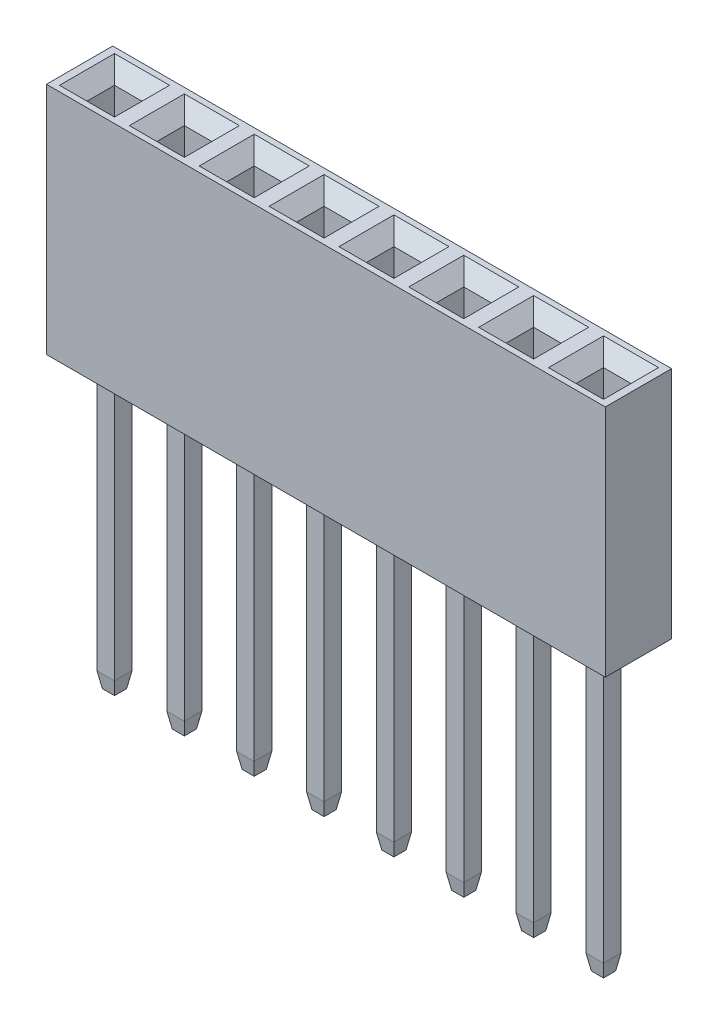
SolidWorks part; units mm, degrees
material "PA Type 6"
ref_plane "Front Plane" through (0, 0, 0) normal (0, 0, 1) x (1, 0, 0)
ref_plane "Top Plane" through (0, 0, 0) normal (0, 1, 0) x (1, 0, 0)
ref_plane "Right Plane" through (0, 0, 0) normal (1, 0, 0) x (0, 0, -1)
ref_plane "Plane1" through (0, -1.65, 0) normal (0, 1, 0) x (1, 0, 0)
sketch "Sketch2" plane through (0, 0, 0) normal (0, 1, 0) x (1, 0, 0)
  line L0 (0, -55) -> (0, 55) construction
  line L1 (-1.27, 1.205) -> (19.05, 1.205)
  line L2 (-1.27, 1.205) -> (-1.27, -1.205)
  line L3 (-1.27, -1.205) -> (19.05, -1.205)
  line L4 (19.05, 1.205) -> (19.05, -1.205)
  line L5 (-55, 0) -> (55, 0) construction
  dimension "D1" = 20.32
  dimension "D2" = 1.27
  dimension "D3" = 2.41
  dimension "D4" = 1.205
extrude "Boss-Extrude1" add sketch "Sketch2" along normal blind 8.51
sketch "Sketch5" plane through (0, 8.51, 0) normal (0, 1, 0) x (1, 0, 0)
  line L0 (-55, 0) -> (55, 0) construction
  line L1 (0.5, 0.5) -> (-0.5, 0.5)
  line L2 (0.5, 0.5) -> (0.5, -0.5)
  line L3 (0.5, -0.5) -> (-0.5, -0.5)
  line L4 (-0.5, 0.5) -> (-0.5, -0.5)
  line L5 (0, -55) -> (0, 55) construction
  dimension "D1" = 0.5
  dimension "D2" = 1
  dimension "D3" = 0.5
extrude "Cut-Extrude1" cut sketch "Sketch5" against normal blind 5
chamfer "Chamfer1" distance 0.5 angle 45 4 edges at (-0.5, 8.51, 0) (0, 8.51, 0.5) (0.5, 8.51, 0) (0, 8.51, -0.5)
pattern_linear "LPattern3" count 8 spacing 2.54 along (1, 0, 0) of "Chamfer1", "Cut-Extrude1"
ref_axis "Axis1" through (0, -11.44, 0) along (0, 1, 0)
sketch "Sketch11" plane through (0, 0, 0) normal (0, -1, 0) x (1, 0, 0)
  line L0 (0, 0) -> (2.54, 0) construction
  line L1 (-0.32, 0.32) -> (0.32, 0.32)
  line L2 (-0.32, 0.32) -> (-0.32, -0.32)
  line L3 (-0.32, -0.32) -> (0.32, -0.32)
  line L4 (0.32, 0.32) -> (0.32, -0.32)
  line L5 (-0.32, 0.32) -> (0.32, -0.32) construction
  line L6 (-0.32, -0.32) -> (0.32, 0.32) construction
  point P0 (0, 0)
  dimension "0.64" = 0.64
sketch "Sketch12" plane through (0, 0, 0) normal (0, 0, 1) x (1, 0, 0)
  line L0 (0, 8.51) -> (0, -10.49) construction
  line L1 (-1.27, 8.51) -> (19.05, 8.51) construction
  dimension "D1" = 19
extrude "Boss-Extrude2" add sketch "Sketch11" along normal blind 9.92
sketch "Sketch13" plane through (0, -9.92, 0) normal (0, -1, 0) x (1, 0, 0)
  line L4 (0.32, -0.32) -> (0.32, 0.32)
  line L5 (0.32, 0.32) -> (-0.32, 0.32)
  line L6 (-0.32, 0.32) -> (-0.32, -0.32)
  line L7 (-0.32, -0.32) -> (0.32, -0.32)
  line L8 (0.32, -0.32) -> (0.32, 0.32)
  line L9 (0.32, 0.32) -> (-0.32, 0.32)
  line L10 (-0.32, 0.32) -> (-0.32, -0.32)
  line L11 (-0.32, -0.32) -> (0.32, -0.32)
  dimension "D1" = 0
ref_plane "Plane2" through (0, -10.49, 0) normal (0, -1, 0) x (-1, 0, 0)
sketch "Sketch14" plane through (0, -10.49, 0) normal (0, -1, 0) x (-1, 0, 0)
  line L1 (-0.22, 0.22) -> (0.22, 0.22)
  line L2 (-0.22, 0.22) -> (-0.22, -0.22)
  line L3 (-0.22, -0.22) -> (0.22, -0.22)
  line L4 (0.22, 0.22) -> (0.22, -0.22)
  line L5 (-0.22, 0.22) -> (0.22, -0.22) construction
  line L6 (-0.22, -0.22) -> (0.22, 0.22) construction
  point P0 (0, 0)
  dimension "D1" = 0.44
loft "Loft1" add profiles "Sketch13", "Sketch14"
pattern_linear "LPattern4" count 8 spacing 2.54 along (1, 0, 0) of "Boss-Extrude2", "Loft1"
equation "\"D1@Sketch2\"=2.54 * 8"
